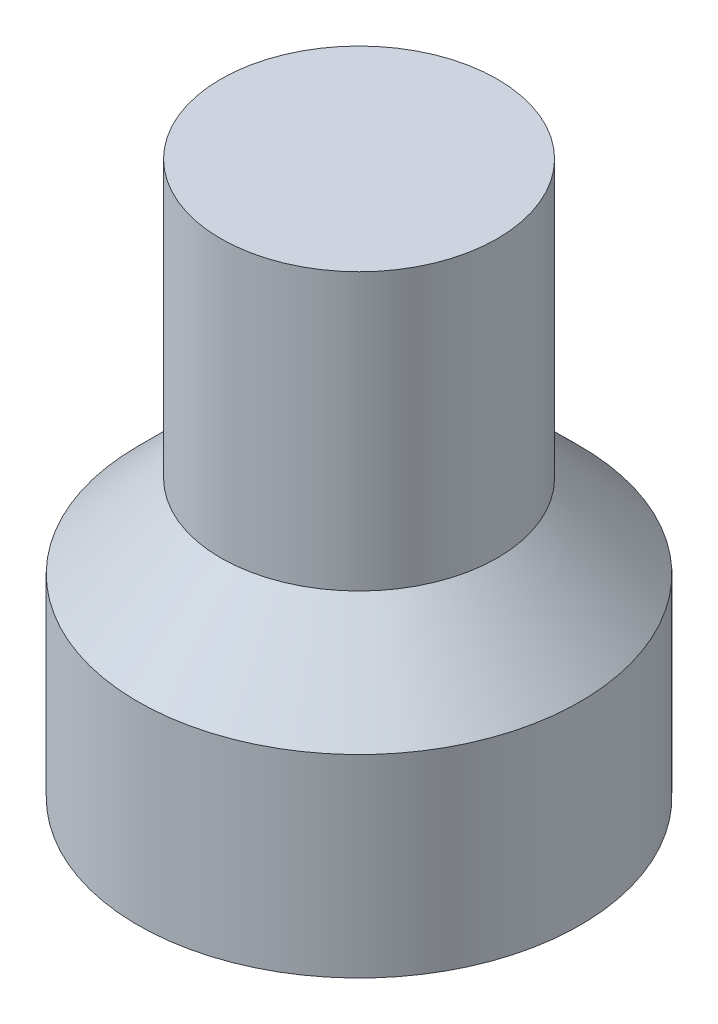
SolidWorks part; units mm, degrees
material "Простая углеродистая сталь"
ref_plane "Front" through (0, 0, 0) normal (0, 0, 1) x (1, 0, 0)
ref_plane "Top" through (0, 0, 0) normal (0, 1, 0) x (1, 0, 0)
ref_plane "Right" through (0, 0, 0) normal (1, 0, 0) x (0, 0, -1)
sketch "Эскиз1" plane through (0, 0, 0) normal (0, 0, 1) x (1, 0, 0)
  line L1 (0, 10) -> (-5, 10)
  line L9 (0, -10) -> (-8, -10)
  line L10 (0, 10) -> (0, -10)
  line L11 (-8, -10) -> (-8, 0)
  line L12 (-8, 0) -> (-5, 0)
  line L13 (-5, 0) -> (-5, 10)
  point P0 (0, 0)
  dimension "D1" = 10
  dimension "D2" = 8
  dimension "D5" = 5
  dimension "D6" = 20
revolve "База" add sketch "Эскиз1" angle 360 about L10
chamfer "Фаска1" distance 3 angle 45 1 edges at (-8, 0, 0)
sketch "Эскиз4" plane through (0, -10, 0) normal (0, -1, 0) x (1, 0, 0)
  circle A0 centre (0, 0) radius 5.1
  dimension "D1" = 10.2
extrude "Вырез-Вытянуть1" cut sketch "Эскиз4" against normal blind 5.1
hole_wizard "Крепление магнита M3" positions "Эскиз2" profile "Эскиз3" tap size "M3" standard "ISO"
sketch "Эскиз2" plane through (0, -4.9, 0) normal (0, -1, 0) x (-1, 0, 0)
  point P0 (0, 0)
cosmetic thread "Отверстие резьбы1"
sketch "Эскиз3" plane through (0, -4.9, 0) normal (1, 0, 0) x (0, 0, -1)
  line L0 (0, 0) -> (0, 10.7511)
  line L1 (0, 10.7511) -> (1.25, 10)
  line L2 (1.25, 10) -> (1.25, 0)
  line L5 (1.25, 0) -> (0, 0)
  line L10 (0, 10.7511) -> (-1.25, 10) construction
  line L11 (0, -6.35) -> (0, 107.95) construction
  dimension "Диаметр сверла" = 2.5
  dimension "Глубина сверла" = 10
  dimension "Угол заточки сверла" = 118
